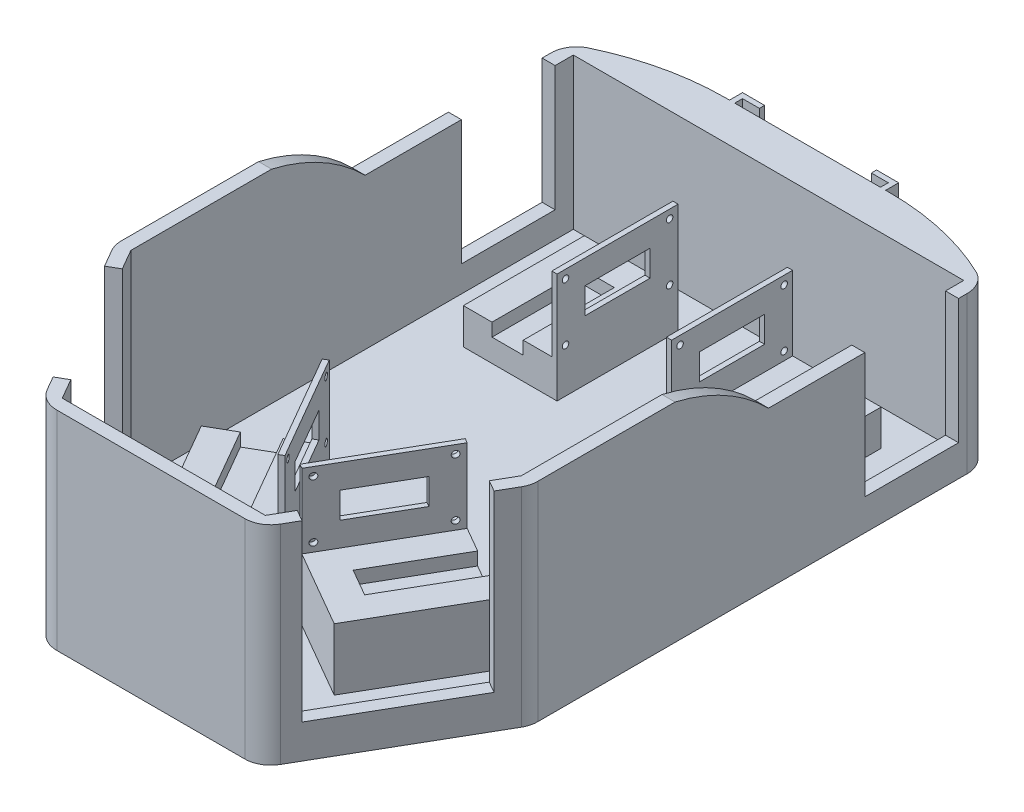
SolidWorks part; units mm, degrees
ref_plane "Front Plane" through (0, 0, 0) normal (0, 0, 1) x (1, 0, 0)
ref_plane "Top Plane" through (0, 0, 0) normal (0, 1, 0) x (1, 0, 0)
ref_plane "Right Plane" through (0, 0, 0) normal (1, 0, 0) x (0, 0, -1)
sketch "Sketch1" plane through (0, 0, 0) normal (0, 1, 0) x (1, 0, 0)
  line L7 (0, 0) -> (0, -170)
  line L8 (0, 0) -> (150, 0)
  line L9 (150, 0) -> (150, -170)
  line L10 (150, -170) -> (114, -232.3538)
  line L11 (0, -170) -> (36, -232.3538)
  line L12 (36, -232.3538) -> (114, -232.3538)
  line L13 (-5, 5) -> (-5, -171.3397)
  line L14 (-5, -171.3397) -> (33.1132, -237.3538)
  line L15 (33.1132, -237.3538) -> (116.8868, -237.3538)
  line L16 (155, -171.3397) -> (116.8868, -237.3538)
  line L17 (155, 5) -> (155, -171.3397)
  line L18 (-5, 5) -> (155, 5)
  dimension "D1" = 170
  dimension "D2" = 150
  dimension "D3" = 72
  dimension "D4" = 30
  dimension "D5" = 30
  dimension "D6" = 72
  dimension "D7" = 5
extrude "Boss-Extrude1" add sketch "Sketch1" along normal blind 80 contours L9 L10 L12 L11 L7 L8 | L13 L14 L15 L16 L17 L18
sketch "Sketch8" plane through (0, 0, 0) normal (0, -1, 0) x (1, 0, 0)
  line L0 (0, 0) -> (0, 170)
  line L1 (0, 170) -> (36, 232.3538)
  line L2 (36, 232.3538) -> (114, 232.3538)
  line L3 (114, 232.3538) -> (150, 170)
  line L4 (150, 170) -> (150, 0)
  line L5 (150, 0) -> (0, 0)
extrude "Boss-Extrude2" add sketch "Sketch8" against normal blind 2 separate body
sketch "Sketch9" plane through (0, 2, 0) normal (0, 1, 0) x (1, 0, 0)
  line L0 (0, 0) -> (150, 0) construction
  line L1 (98, -13.75) -> (132, -13.75)
  line L2 (98, -13.75) -> (98, -60.25)
  line L3 (98, -60.25) -> (132, -60.25)
  line L4 (132, -13.75) -> (132, -60.25)
  line L5 (150, 0) -> (150, -170) construction
  dimension "D1" = 46.5
  dimension "D2" = 34
  dimension "D3" = 13.75
  dimension "D4" = 18
extrude "Boss-Extrude3" add sketch "Sketch9" along normal blind 13.75
sketch "Sketch13" plane through (98, 0, 0) normal (-1, 0, 0) x (0, 0, 1)
  line L1 (13.75, 2) -> (60.25, 2)
  line L2 (13.75, 2) -> (13.75, 44.25)
  line L3 (13.75, 44.25) -> (60.25, 44.25)
  line L4 (60.25, 2) -> (60.25, 44.25)
  dimension "D1" = 42.25
  dimension "D2" = 46.5
extrude "Boss-Extrude7" add sketch "Sketch13" along normal blind 2
sketch "Sketch14" plane through (96, 0, 0) normal (-1, 0, 0) x (0, 0, 1)
  line L0 (13.75, 44.25) -> (13.75, 2) construction
  line L1 (60.25, 44.25) -> (13.75, 44.25) construction
  line L2 (60.25, 2) -> (60.25, 44.25) construction
  line L3 (13.75, 30) -> (60.25, 30) construction
  line L5 (24.5, 35) -> (49.5, 35)
  line L6 (24.5, 35) -> (24.5, 25)
  line L7 (24.5, 25) -> (49.5, 25)
  line L8 (49.5, 35) -> (49.5, 25)
  circle A0 centre (17, 41) radius 1.25
  circle A1 centre (57, 41) radius 1.25
  circle A2 centre (57, 19) radius 1.25
  circle A3 centre (17, 19) radius 1.25
  dimension "D1" = 2.5
  dimension "D2" = 3.25
  dimension "D3" = 3.25
  dimension "D4" = 3.25
  dimension "D5" = 3.25
  dimension "D6" = 14.25
  dimension "D7" = 10
  dimension "D8" = 25
  dimension "D9" = 5
  dimension "D10" = 10.75
extrude "Cut-Extrude1" cut sketch "Sketch14" against normal blind 2
sketch "Sketch15" plane through (0, 15.75, 0) normal (0, 1, 0) x (1, 0, 0)
  line L0 (98, -60.25) -> (132, -60.25) construction
  line L1 (109, -25.25) -> (121, -25.25)
  line L2 (109, -25.25) -> (109, -60.25)
  line L3 (109, -60.25) -> (121, -60.25)
  line L4 (121, -25.25) -> (121, -60.25)
  line L5 (132, -60.25) -> (132, -13.75) construction
  dimension "D1" = 12
  dimension "D2" = 35
  dimension "D3" = 0
  dimension "D4" = 11
extrude "Cut-Extrude2" cut sketch "Sketch15" against normal blind 5
sketch "Sketch17" plane through (155, 0, 0) normal (1, 0, 0) x (0, 0, -1)
  line L0 (5, 0) -> (-171.3397, 0) construction
  line L1 (5, 80) -> (5, 0) construction
  line L2 (5, 60) -> (-80, 60)
  line L3 (-115.9346, 80) -> (5, 80)
  line L4 (5, 80) -> (5, 60)
  arc A0 (-80, 60) -> (-115.9346, 80) centre (-132.8191, 7.3808) ccw
  dimension "D1" = 85
  dimension "D2" = 60
extrude "Cut-Extrude3" cut sketch "Sketch17" against normal through all
fillet "Fillet5" radius 10 4 edges at (-5, 40, 171.3397) (155, 40, 171.3397) (116.8868, 40, 237.3538) (33.1132, 40, 237.3538)
sketch "Sketch16" plane through (150, 0, 0) normal (-1, 0, 0) x (0, 0, 1)
  line L0 (80, 60) -> (0, 60) construction
  line L1 (7, 12) -> (43, 12)
  line L2 (7, 12) -> (7, 60)
  line L3 (7, 60) -> (43, 60)
  line L4 (43, 12) -> (43, 60)
  line L5 (0, 60) -> (0, 2) construction
  dimension "D1" = 36
  dimension "D2" = 48
  dimension "D3" = 7
  dimension "0" = 0
extrude "Cut-Extrude4" cut sketch "Sketch16" against normal blind 5
sketch "Sketch38" plane through (0, 2, 0) normal (0, 1, 0) x (1, 0, 0)
  line L5 (109.0545, -200.9197) -> (132.3045, -160.6495)
  line L9 (150, -170) -> (114, -232.3538) construction
  line L10 (109.0545, -200.9197) -> (79.6096, -183.9197)
  line L12 (79.6096, -183.9197) -> (102.8596, -143.6495)
  line L13 (102.8596, -143.6495) -> (132.3045, -160.6495)
  dimension "D1" = 20
  dimension "D2" = 46.5
  dimension "D3" = 90
  dimension "D4" = 34
  dimension "D5" = 46.5
  dimension "0" = 0
  dimension "D6" = 90
  dimension "0.75" = 0.75
extrude "Boss-Extrude16" add sketch "Sketch38" along normal blind 23.75
sketch "Sketch39" plane through (139.3468, 0, 80.4519) normal (-0.866, 0, -0.5) x (-0.5, 0, 0.866)
  line L1 (72.9743, 2) -> (119.4743, 2)
  line L2 (72.9743, 2) -> (72.9743, 54.25)
  line L3 (72.9743, 54.25) -> (119.4743, 54.25)
  line L4 (119.4743, 2) -> (119.4743, 54.25)
  dimension "D1" = 46.5
  dimension "D2" = 52.25
extrude "Boss-Extrude17" add sketch "Sketch39" along normal blind 2
sketch "Sketch40" plane through (137.6147, 0, 79.4519) normal (-0.866, 0, -0.5) x (-0.5, 0, 0.866)
  line L0 (119.4743, 54.25) -> (72.9743, 54.25) construction
  line L1 (72.9743, 54.25) -> (72.9743, 2) construction
  line L2 (96.2243, 2) -> (96.2243, 54.25) construction
  line L4 (72.9743, 40) -> (119.4743, 40) construction
  line L5 (119.4743, 2) -> (119.4743, 54.25) construction
  line L6 (72.9743, 2) -> (119.4743, 2) construction
  line L8 (83.7243, 45) -> (108.7243, 45)
  line L9 (83.7243, 45) -> (83.7243, 35)
  line L10 (83.7243, 35) -> (108.7243, 35)
  line L11 (108.7243, 45) -> (108.7243, 35)
  circle A0 centre (76.2243, 51) radius 1.25
  circle A1 centre (116.2243, 51) radius 1.25
  circle A2 centre (116.2243, 29) radius 1.25
  circle A3 centre (76.2243, 29) radius 1.25
  dimension "D1" = 2.5
  dimension "D2" = 3.25
  dimension "D3" = 3.25
  dimension "D4" = 14.25
  dimension "D5" = 23.25
  dimension "D6" = 25
  dimension "D7" = 10
  dimension "D8" = 5
  dimension "D9" = 12.5
extrude "Cut-Extrude10" cut sketch "Sketch40" against normal blind 2
sketch "Sketch42" plane through (0, 25.75, 0) normal (0, 1, 0) x (1, 0, 0)
  line L0 (105.2782, -185.4604) -> (122.7782, -155.1495)
  line L1 (109.0545, -200.9197) -> (132.3045, -160.6495) construction
  line L2 (105.2782, -185.4604) -> (94.8859, -179.4604)
  line L3 (94.8859, -179.4604) -> (112.3859, -149.1495)
  line L4 (112.3859, -149.1495) -> (122.7782, -155.1495)
  line L5 (132.3045, -160.6495) -> (102.8596, -143.6495) construction
  dimension "D1" = 0
  dimension "11" = 11
  dimension "D2" = 12
  dimension "D3" = 35
  dimension "D4" = 0
extrude "Cut-Extrude11" cut sketch "Sketch42" against normal blind 5
sketch "Sketch43" plane through (186.1122, 0, 107.4519) normal (-0.866, 0, -0.5) x (-0.5, 0, 0.866)
  line L0 (72.2243, 80) -> (144.2243, 80) construction
  line L1 (81.2243, 80) -> (135.2243, 80)
  line L2 (81.2243, 80) -> (81.2243, 13)
  line L3 (81.2243, 13) -> (135.2243, 13)
  line L4 (135.2243, 80) -> (135.2243, 13)
  line L5 (72.2243, 80) -> (72.2243, 2) construction
  dimension "D1" = 54
  dimension "D2" = 67
  dimension "D3" = 9
extrude "Cut-Extrude12" cut sketch "Sketch43" against normal blind 5
ref_plane "Plane3" through (75, 0, 0) normal (-1, 0, 0) x (0, 0, 1)
mirror "Mirror1" about plane through (75, 0, 0) normal (-1, 0, 0) of "Cut-Extrude1", "Boss-Extrude3", "Cut-Extrude2", "Boss-Extrude7", "Boss-Extrude16", "Boss-Extrude17", "Cut-Extrude11", "Cut-Extrude10", "Cut-Extrude4", "Cut-Extrude12"
sketch "Sketch44" plane through (0, 60, 0) normal (0, 1, 0) x (1, 0, 0)
  line L0 (0, -7) -> (0, 0) construction
  line L1 (0, 15) -> (150, 15)
  line L2 (0, 15) -> (0, 5)
  line L3 (0, 5) -> (150, 5)
  line L4 (150, 15) -> (150, 5)
  line L5 (-5, 5) -> (155, 5) construction
  dimension "D1" = 150
  dimension "D2" = 10
  dimension "D3" = 0
  dimension "D4" = 0
extrude "Boss-Extrude18" add sketch "Sketch44" against normal blind 60
sketch "Sketch45" plane through (0, 0, -15) normal (0, 0, -1) x (-1, 0, 0)
  line L1 (5, 60) -> (5, 0) construction
  line L2 (-105, 60) -> (-45, 60)
  line L3 (-105, 60) -> (-105, 0)
  line L4 (-105, 0) -> (-45, 0)
  line L5 (-45, 60) -> (-45, 0)
  line L6 (-150, 0) -> (0, 0) construction
  dimension "D1" = 60
  dimension "D2" = 60
  dimension "D3" = 50
  dimension "D4" = 0
extrude "Boss-Extrude19" add sketch "Sketch45" along normal blind 5
fillet "Fillet8" radius 10 2 edges at (155, 30, -5) (-5, 30, -5)
fillet "Fillet9" radius 100 2 edges at (150, 30, -15) (0, 30, -15)
sketch "Sketch46" plane through (0, 60, 0) normal (0, 1, 0) x (1, 0, 0)
  line L0 (53.5, 20) -> (96.5, 20)
  line L1 (45, 20) -> (105, 20) construction
  line L2 (105, 20) -> (105, 15) construction
  line L3 (53.5, 20) -> (53.5, 18)
  line L4 (96.5, 20) -> (96.5, 18)
  line L5 (96.5, 18) -> (103, 18)
  line L6 (103, 18) -> (103, 15)
  line L7 (75, 26.9684) -> (75, 14.7019) construction
  line L8 (45, 20) -> (45, 15) construction
  line L9 (103, 15) -> (47, 15)
  line L10 (47, 18) -> (47, 15)
  line L11 (53.5, 18) -> (47, 18)
  point P16 (75, 15)
  dimension "D2" = 8.5
  dimension "D3" = 2
  dimension "D4" = 6.5
  dimension "D5" = 3
  dimension "D6" = 30
extrude "Cut-Extrude13" cut sketch "Sketch46" against normal blind 51
sketch "Sketch48" plane through (0, 9, 0) normal (0, 1, 0) x (1, 0, 0)
  line L1 (47, 18) -> (103, 18)
  line L2 (47, 18) -> (47, 15)
  line L3 (47, 15) -> (103, 15)
  line L4 (103, 18) -> (103, 15)
  dimension "D1" = 56
  dimension "D2" = 3
extrude "Cut-Extrude14" cut sketch "Sketch48" against normal blind 7
